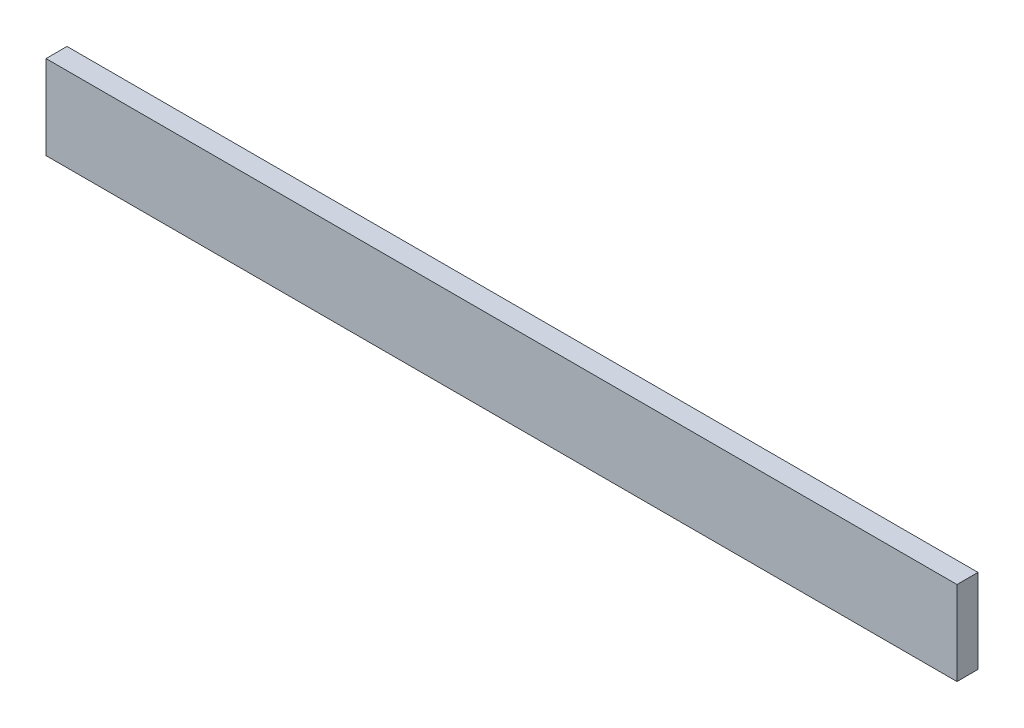
SolidWorks part; units mm, degrees
ref_plane "Front Plane" through (0, 0, 0) normal (0, 0, 1) x (1, 0, 0)
ref_plane "Top Plane" through (0, 0, 0) normal (0, 1, 0) x (1, 0, 0)
ref_plane "Right Plane" through (0, 0, 0) normal (1, 0, 0) x (0, 0, -1)
sketch "Sketch2" plane through (0, 0, 0) normal (0, 0, 1) x (1, 0, 0)
  line L1 (-47.8692, 21.2481) -> (206.1308, 21.2481)
  line L2 (-47.8692, 21.2481) -> (-47.8692, 8.5481)
  line L3 (-47.8692, 8.5481) -> (206.1308, 8.5481)
  line L4 (206.1308, 21.2481) -> (206.1308, 8.5481)
  line L5 (206.1308, 8.5481) -> (502.623, 8.5481)
  line L6 (206.1308, 8.5481) -> (206.1308, 21.2481)
  line L7 (206.1308, 21.2481) -> (502.623, 21.2481)
  line L8 (502.623, 8.5481) -> (502.623, 21.2481)
  dimension "D1" = 12.7
  dimension "D2" = 254
extrude "Boss-Extrude1" add sketch "Sketch2" along normal blind 50.8 contours L4 L1 L2 L3 | L5 L8 L7 L4 region at (79.1308, 14.8981, 0) region at (354.3769, 14.8981, 0)
sketch "Sketch3" plane through (0, 21.2481, 0) normal (0, 1, 0) x (1, 0, 0)
  circle A0 centre (79.1308, -28.4831) radius 17.1408
extrude "Boss-Extrude2" [suppressed] add sketch "Sketch3" along normal blind 19.05
sketch "Sketch4" [suppressed] plane through (0, 40.2981, 0) normal (0, 1, 0) x (1, 0, 0)
  line L1 (50.7675, -8.111) -> (126.0034, -8.111)
  line L2 (50.7675, -8.111) -> (50.7675, -48.0661)
  line L3 (50.7675, -48.0661) -> (126.0034, -48.0661)
  line L4 (126.0034, -8.111) -> (126.0034, -48.0661)
extrude "Boss-Extrude3" [suppressed] add sketch "Sketch4" along normal blind 38.1
scale "Scale2" scale about centroid uniform scaling yes scale factor 0.06
move or copy body "rotate" bodies to move or copy 105 copy no rotation origin (0, 33.6669, 26.5501) rotation axis (1, 0, 0) rotation angle 90
scale "Scale5" scale about centroid uniform scaling yes scale factor 0.25
move or copy body "-4 x" bodies to move or copy 111 copy no translate (-101.6, 0, 0)
move or copy body "-2 y" bodies to move or copy 117 copy no translate (0, -55.88, 0)
scale "Scale6" bodies to scale 121 scale about centroid uniform scaling yes scale factor 0.25
move or copy body "-2.1z" bodies to move or copy 122 copy no translate (0, 0, -30.48)
